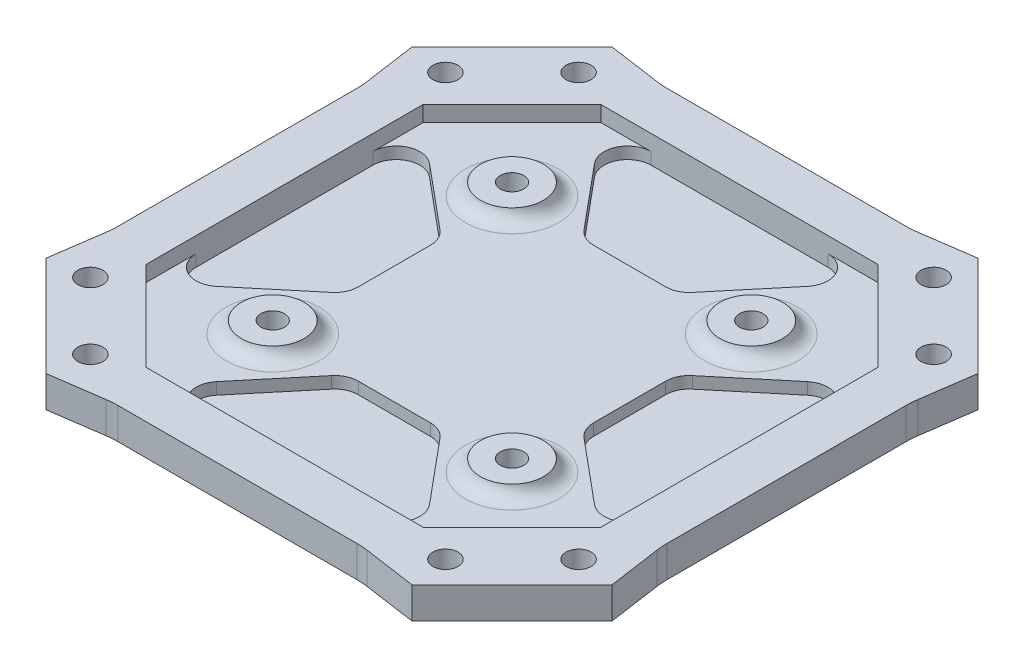
SolidWorks part; units mm, degrees
ref_plane "Front Plane" through (0, 0, 0) normal (0, 0, 1) x (1, 0, 0)
ref_plane "Top Plane" through (0, 0, 0) normal (0, 1, 0) x (1, 0, 0)
ref_plane "Right Plane" through (0, 0, 0) normal (1, 0, 0) x (0, 0, -1)
sketch "Sketch1" plane through (0, 0, 0) normal (0, 1, 0) x (1, 0, 0)
  line L0 (0, 0) -> (84.8528, 84.8528) construction
  line L5 (35, -35) -> (-35, 35) construction
  line L6 (35, 35) -> (-35, -35) construction
  line L7 (0, -62.8714) -> (0, 35) construction
  line L8 (15.934, 35) -> (-15.934, 35)
  line L9 (35, -15.934) -> (35, 15.934)
  line L10 (-15.934, -35) -> (15.934, -35)
  line L11 (-35, 15.934) -> (-35, -15.934)
  line L12 (20.5061, 33.234) -> (33.234, 20.5061) construction
  line L13 (36.0624, 23.3345) -> (23.3345, 36.0624)
  line L14 (15.934, 35) -> (23.3345, 36.0624)
  line L15 (35, 15.934) -> (36.0624, 23.3345)
  line L16 (15.934, -35) -> (23.3345, -36.0624)
  line L17 (23.3345, -36.0624) -> (36.0624, -23.3345)
  line L18 (35, -15.934) -> (36.0624, -23.3345)
  line L19 (-35, -15.934) -> (-36.0624, -23.3345)
  line L20 (-36.0624, -23.3345) -> (-23.3345, -36.0624)
  line L21 (-15.934, -35) -> (-23.3345, -36.0624)
  line L22 (-15.934, 35) -> (-23.3345, 36.0624)
  line L23 (-23.3345, 36.0624) -> (-36.0624, 23.3345)
  line L24 (-35, 15.934) -> (-36.0624, 23.3345)
  circle A0 centre (22.6274, 31.1127) radius 1.6
  circle A1 centre (31.1127, 22.6274) radius 1.6
  circle A2 centre (22.6274, -31.1127) radius 1.6
  circle A3 centre (31.1127, -22.6274) radius 1.6
  circle A4 centre (-31.1127, -22.6274) radius 1.6
  circle A5 centre (-22.6274, -31.1127) radius 1.6
  circle A6 centre (-22.6274, 31.1127) radius 1.6
  circle A7 centre (-31.1127, 22.6274) radius 1.6
  point P0 (0, 0)
  point P13 (0, 35)
  point P22 (0, 0)
  point P29 (29.6985, 29.6985)
  point P56 (0, 0)
  dimension "D10" = 3.2
  dimension "D11" = 3.2
  dimension "D12" = 6
  dimension "D13" = 6
  dimension "D1" = 70
  dimension "D2" = 70
  dimension "D3" = 120
  dimension "D5" = 18
  dimension "D6" = 9
  dimension "D7" = 82
  dimension "D8" = 18
  dimension "D9" = 4
  dimension "D4" = 4
  dimension "D14" = 4
extrude "Boss-Extrude1" add sketch "Sketch1" along normal blind 4
sketch "Sketch2" plane through (0, 4, 0) normal (0, 1, 0) x (1, 0, 0)
  line L0 (0, 35) -> (0, 0) construction
  line L1 (15.934, 35) -> (-15.934, 35) construction
  line L2 (0, 0) -> (-35, 0) construction
  line L3 (-35, 15.934) -> (-35, -15.934) construction
  line L4 (-17.669, 29) -> (17.669, 29)
  line L5 (17.669, 29) -> (29, 17.669)
  line L6 (29, 17.669) -> (29, -17.669)
  line L7 (29, -17.669) -> (17.669, -29)
  line L8 (17.669, -29) -> (-17.669, -29)
  line L9 (-17.669, -29) -> (-29, -17.669)
  line L10 (-29, -17.669) -> (-29, 17.669)
  line L11 (-29, 17.669) -> (-17.669, 29)
  line L12 (-15.934, -35) -> (15.934, -35) construction
  line L13 (-36.0624, -23.3345) -> (-23.3345, -36.0624) construction
  line L14 (23.3345, -36.0624) -> (36.0624, -23.3345) construction
  point P11 (0, 29)
  point P24 (23.3345, -23.3345)
  dimension "D1" = 6
  dimension "D2" = 6
  dimension "D3" = 9
  dimension "D4" = 9
extrude "Cut-Extrude1" cut sketch "Sketch2" against normal blind 2
sketch "Sketch3" plane through (0, 2, 0) normal (0, 1, 0) x (1, 0, 0)
  line L0 (0, 29) -> (0, 0) construction
  line L1 (17.669, 29) -> (-17.669, 29) construction
  line L2 (0, 0) -> (-29, 0) construction
  line L3 (-29, 17.669) -> (-29, -17.669) construction
  line L4 (-15, -4.5951) -> (-15, 4.5951)
  line L5 (-16.0792, 6.8995) -> (-24.0792, 13.5676)
  line L6 (-29, 11.2631) -> (-29, -11.2631)
  line L7 (-24.0792, -13.5676) -> (-16.0792, -6.8995)
  line L8 (-13.5676, 24.0792) -> (-6.8995, 16.0792)
  line L9 (11.2631, 29) -> (-11.2631, 29)
  line L10 (6.8995, 16.0792) -> (13.5676, 24.0792)
  line L11 (-4.5951, 15) -> (4.5951, 15)
  line L12 (24.0792, 13.5676) -> (16.0792, 6.8995)
  line L13 (29, -11.2631) -> (29, 11.2631)
  line L14 (16.0792, -6.8995) -> (24.0792, -13.5676)
  line L15 (15, 4.5951) -> (15, -4.5951)
  line L16 (13.5676, -24.0792) -> (6.8995, -16.0792)
  line L17 (-11.2631, -29) -> (11.2631, -29)
  line L18 (-6.8995, -16.0792) -> (-13.5676, -24.0792)
  line L19 (4.5951, -15) -> (-4.5951, -15)
  arc A0 (-15, 4.5951) -> (-16.0792, 6.8995) centre (-18, 4.5951) ccw
  arc A1 (-15, -4.5951) -> (-16.0792, -6.8995) centre (-18, -4.5951) cw
  arc A2 (-29, -11.2631) -> (-24.0792, -13.5676) centre (-26, -11.2631) ccw
  arc A3 (-24.0792, 13.5676) -> (-29, 11.2631) centre (-26, 11.2631) ccw
  arc A4 (-11.2631, 29) -> (-13.5676, 24.0792) centre (-11.2631, 26) ccw
  arc A5 (13.5676, 24.0792) -> (11.2631, 29) centre (11.2631, 26) ccw
  arc A6 (4.5951, 15) -> (6.8995, 16.0792) centre (4.5951, 18) ccw
  arc A7 (-4.5951, 15) -> (-6.8995, 16.0792) centre (-4.5951, 18) cw
  arc A8 (29, 11.2631) -> (24.0792, 13.5676) centre (26, 11.2631) ccw
  arc A9 (24.0792, -13.5676) -> (29, -11.2631) centre (26, -11.2631) ccw
  arc A10 (15, -4.5951) -> (16.0792, -6.8995) centre (18, -4.5951) ccw
  arc A11 (15, 4.5951) -> (16.0792, 6.8995) centre (18, 4.5951) cw
  arc A12 (11.2631, -29) -> (13.5676, -24.0792) centre (11.2631, -26) ccw
  arc A13 (-13.5676, -24.0792) -> (-11.2631, -29) centre (-11.2631, -26) ccw
  arc A14 (-4.5951, -15) -> (-6.8995, -16.0792) centre (-4.5951, -18) ccw
  arc A15 (4.5951, -15) -> (6.8995, -16.0792) centre (4.5951, -18) cw
  point P11 (-15, 0)
  point P17 (-15, 6)
  point P20 (-15, -6)
  point P23 (-29, -17.669)
  point P26 (-29, 17.669)
  point P66 (0, 0)
  dimension "D3" = 3
  dimension "D1" = 15
  dimension "D2" = 12
  dimension "D4" = 4
extrude "Cut-Extrude2" cut sketch "Sketch3" against normal blind 1.5
sketch "Sketch4" plane through (0, 2, 0) normal (0, 1, 0) x (1, 0, 0)
  line L1 (0, 0) -> (15.25, 0) construction
  line L2 (0, 0) -> (0, 15.25) construction
  line L3 (0, 15.25) -> (15.25, 15.25) construction
  line L4 (15.25, 0) -> (15.25, 15.25) construction
  circle A0 centre (15.25, 15.25) radius 1.5
  dimension "D2" = 3
  dimension "D1" = 15.25
extrude "Cut-Extrude3" cut sketch "Sketch4" against normal through all
sketch "Sketch5" plane through (0, 2, 0) normal (0, 1, 0) x (1, 0, 0)
  circle A0 centre (15.25, 15.25) radius 4
  circle A1 centre (15.25, 15.25) radius 1.5 construction
  circle A2 centre (15.25, 15.25) radius 1.5
  dimension "D1" = 8
extrude "Boss-Extrude4" add sketch "Sketch5" along normal blind 1.5
ref_axis "Axis1" through (0, -0.2, 0) along (0, 1, 0)
pattern_circular "CirPattern1" count 4 over 360 about axis through (0, -0.2, 0) along (0, 1, 0) of "Cut-Extrude3", "Boss-Extrude4"
fillet "Fillet1" radius 2 4 edges at (15.25, 2, 11.25) (15.25, 2, -19.25) (-15.25, 2, -19.25) (-15.25, 2, 11.25)
fillet "Fillet2" radius 10 8 edges at (-15.934, 2, -35) (15.934, 2, -35) (35, 2, -15.934) (35, 2, 15.934) (-35, 2, -15.934) (-35, 2, 15.934) (15.934, 2, 35) (-15.934, 2, 35)
